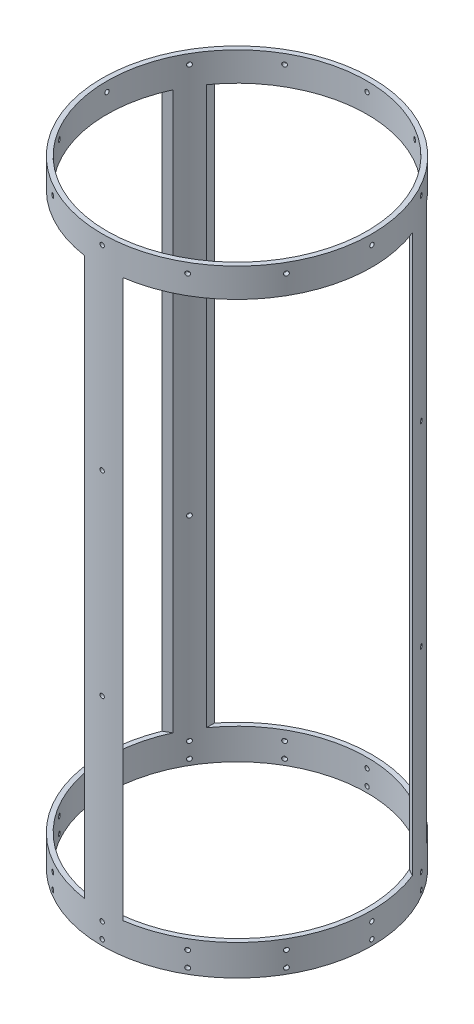
SolidWorks part; units mm, degrees
material "6061-T6 (SS)"
ref_plane "Front Plane" through (0, 0, 0) normal (0, 0, 1) x (1, 0, 0)
ref_plane "Top Plane" through (0, 0, 0) normal (0, 1, 0) x (1, 0, 0)
ref_plane "Right Plane" through (0, 0, 0) normal (1, 0, 0) x (0, 0, -1)
sketch "Sketch1" plane through (0, 0, 0) normal (0, 1, 0) x (1, 0, 0)
  circle A0 centre (0, 0) radius 88.9
  circle A1 centre (0, 0) radius 85.725
  dimension "D1" = 177.8
  dimension "D2" = 171.45
extrude "Boss-Extrude1" add sketch "Sketch1" along normal mid plane 406.4
sketch "Sketch2" plane through (0, 0, 0) normal (0, 0, 1) x (1, 0, 0)
  line L0 (85.725, 203.2) -> (-85.725, 203.2) construction
  line L1 (-69.85, -182.88) -> (69.85, -182.88)
  line L2 (-69.85, -182.88) -> (-69.85, 184.15)
  line L3 (-69.85, 184.15) -> (69.85, 184.15)
  line L4 (69.85, -182.88) -> (69.85, 184.15)
  line L5 (-69.85, -182.88) -> (69.85, 184.15) construction
  line L6 (-69.85, 184.15) -> (69.85, -182.88) construction
  line L7 (88.9, -203.2) -> (88.9, 203.2) construction
  line L8 (-88.9, 203.2) -> (-88.9, -203.2) construction
  line L9 (-88.9, -203.2) -> (88.9, -203.2) construction
  point P0 (0, 0)
  dimension "D1" = 19.05
  dimension "D2" = 19.05
  dimension "D3" = 19.05
  dimension "D4" = 20.32
extrude "Cut-Extrude1" cut sketch "Sketch2" against normal up to surface (54.9926 mm away) up to face at (0, 203.2, 88.9)
pattern_circular "CirPattern1" count 3 over 360 about axis through (0, 203.2, 0) along (0, -1, 0) of "Cut-Extrude1"
ref_plane "Plane1" through (88.9, 0, 0) normal (1, 0, 0) x (0, 0, -1)
sketch "Sketch3" plane through (88.9, 0, 0) normal (1, 0, 0) x (0, 0, -1)
  line L0 (32.9956, -182.88) -> (-87.9882, -182.88) construction
  line L1 (-88.9, -203.2) -> (88.9, -203.2) construction
  circle A0 centre (0, -199.39) radius 1.4351
  circle A1 centre (0, -189.23) radius 1.4351
  dimension "D1" = 3.81
  dimension "D2" = 2.8702
  dimension "D3" = 2.8702
  dimension "D4" = 6.35
extrude "Cut-Extrude2" cut sketch "Sketch3" against normal blind 15.24
pattern_circular "CirPattern2" count 12 over 360 about axis through (0, 203.2, 0) along (0, -1, 0) of "Cut-Extrude2" reverse direction yes
sketch "Sketch4" plane through (88.9, 0, 0) normal (1, 0, 0) x (0, 0, -1)
  line L0 (0, 97.79) -> (0, -97.79) construction
  line L1 (88.9, 203.2) -> (-88.9, 203.2) construction
  circle A0 centre (0, 196.85) radius 1.4351
  dimension "D1" = 2.8702
  dimension "D2" = 6.35
extrude "Cut-Extrude3" cut sketch "Sketch4" against normal blind 15.24
pattern_circular "CirPattern3" count 12 over 360 about axis through (0, 203.2, 0) along (0, -1, 0) of "Cut-Extrude3"
ref_plane "Plane2" through (0, 0, 88.9) normal (0, 0, 1) x (1, 0, 0)
sketch "Sketch5" plane through (0, 0, 88.9) normal (0, 0, 1) x (1, 0, 0)
  circle A0 centre (0, 68.1736) radius 1.4351
  circle A1 centre (0, -60.5536) radius 1.4351
  circle A2 centre (0, 196.85) radius 1.4351 construction
  circle A3 centre (0, -189.23) radius 1.4351 construction
  dimension "D1" = 128.6764
  dimension "D2" = 128.6764
  dimension "D3" = 2.8702
  dimension "D4" = 2.8702
extrude "Cut-Extrude4" cut sketch "Sketch5" against normal blind 35.56
pattern_circular "CirPattern4" count 3 over 360 about axis through (0, 203.2, 0) along (0, -1, 0) of "Cut-Extrude4"
